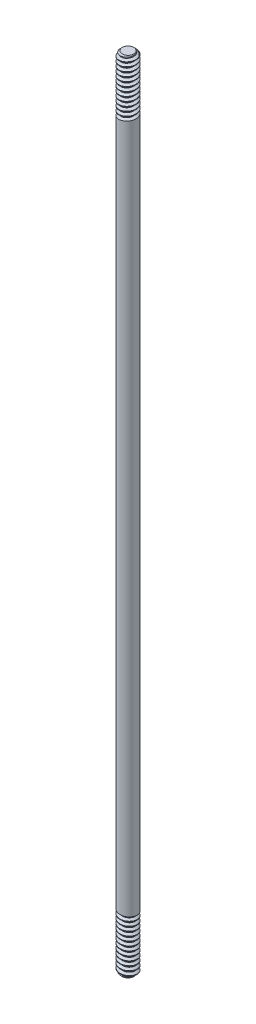
SolidWorks part; units mm, degrees
material "Stop 1060"
ref_plane "Płaszczyzna przednia" through (0, 0, 0) normal (0, 0, 1) x (1, 0, 0)
ref_plane "Płaszczyzna górna" through (0, 0, 0) normal (0, 1, 0) x (1, 0, 0)
ref_plane "Płaszczyzna prawa" through (0, 0, 0) normal (1, 0, 0) x (0, 0, -1)
sketch "Szkic1" plane through (0, 0, 0) normal (0, 1, 0) x (1, 0, 0)
  circle A0 centre (0, 0) radius 3
  point P2 (0, 0)
  dimension "D1" = 6
extrude "Dodanie-wyciągnięcie1" add sketch "Szkic1" along normal blind 140
chamfer "Sfazowanie3" distance 1 angle 45 1 edges at (0, 140, 3)
thread "Gwint1" pitch 1.5 method cut trim with start face yes profile "Profil gwintu1" start angle 0, offset 1, length 20, pitch 1.5, diameter 6
ref_plane "Płaszczyzna1" through (-3, 141, 0) normal (0, 0, 1) x (-1, 0, 0)
sketch "Profil gwintu1" plane through (-3, 141, 0) normal (0, 0, 1) x (-1, 0, 0)
  line L0 (0, 0) -> (0, 1.5) construction
  line L11 (0, 0) -> (0, 1.3125)
  line L12 (0, 1.3125) -> (-0.8119, 0.8437)
  line L13 (-0.8119, 0.8437) -> (-0.8119, 0.4687)
  line L15 (-0.8119, 0.4687) -> (0, 0)
  line L17 (-0.8119, 0.6562) -> (0, 0.6562) construction
  point P2 (0, 0)
  dimension "Pitch" = 1.5
  dimension "Profile_Angle" = 60
  dimension "Profile_Land" = 0.375
  dimension "Profile_Height" = 0.8119
mirror "Lustro1" about plane through (0, 0, 0) normal (0, 1, 0) of bodies 102
